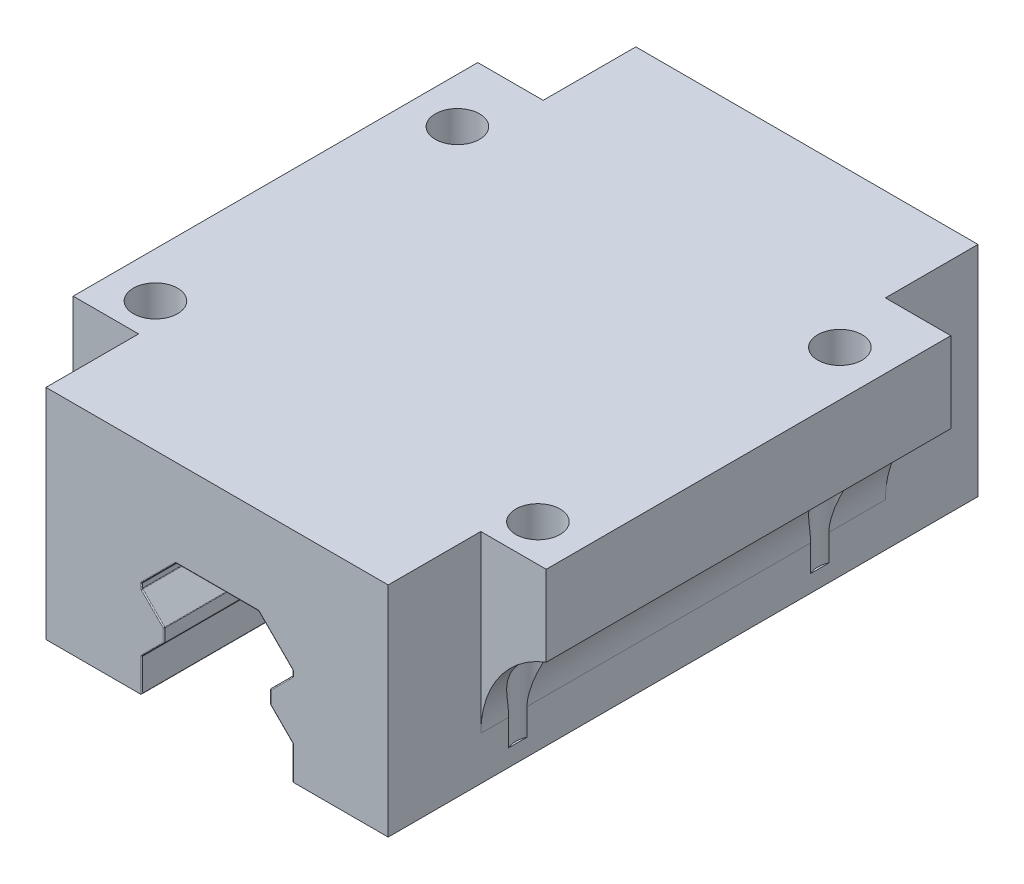
SolidWorks part; units mm, degrees
material "Серое литое железо (SN)"
ref_plane "Спереди" through (0, 0, 0) normal (0, 0, 1) x (1, 0, 0)
ref_plane "Сверху" through (0, 0, 0) normal (0, 1, 0) x (1, 0, 0)
ref_plane "Справа" through (0, 0, 0) normal (1, 0, 0) x (0, 0, -1)
sketch "Эскиз4" plane through (0, 0, 0) normal (0, 0, 1) x (1, 0, 0)
  line L1 (-17, 10.85) -> (17, 10.85)
  line L2 (-17, 10.85) -> (-17, -10.85)
  line L3 (-17, -10.85) -> (17, -10.85)
  line L4 (17, 10.85) -> (17, -10.85)
  line L5 (-17, 10.85) -> (17, -10.85) construction
  line L6 (-17, -10.85) -> (17, 10.85) construction
  point P0 (0, 0)
  dimension "D1" = 34
  dimension "D2" = 21.7
extrude "Бобышка-Вытянуть2" add sketch "Эскиз4" along normal blind 58.6
sketch "Эскиз5" plane through (0, 0, 0) normal (0, 0, -1) x (-1, 0, 0)
  line L0 (0, -10.85) -> (7.5, -10.85)
  line L1 (17, -10.85) -> (-17, -10.85) construction
  line L2 (7.5, -10.85) -> (7.5, -7.55)
  line L3 (7.5, -7.55) -> (5.26, -5.31)
  line L4 (5.26, -5.31) -> (5.26, -3.9893)
  line L5 (5.26, -3.9893) -> (7.5, -1.7493)
  line L6 (7.5, -1.7493) -> (7.5, -1.2493)
  line L7 (7.5, -1.2493) -> (4.1007, 2.15)
  line L8 (4.1007, 2.15) -> (-4.1007, 2.15)
  line L9 (-4.1007, 2.15) -> (-7.5, -1.2493)
  line L10 (-7.5, -1.2493) -> (-7.5, -1.7493)
  line L11 (-7.5, -1.7493) -> (-5.26, -3.9893)
  line L12 (-5.26, -3.9893) -> (-5.26, -5.31)
  line L13 (-5.26, -5.31) -> (-7.5, -7.55)
  line L14 (-7.5, -7.55) -> (-7.5, -10.85)
  line L15 (-7.5, -10.85) -> (0, -10.85)
  dimension "D1" = 7.5
  dimension "D2" = 7.5
  dimension "D3" = 3.3
  dimension "D4" = 135
  dimension "D5" = 135
  dimension "D6" = 135
  dimension "D7" = 135
  dimension "D8" = 135
  dimension "D9" = 135
  dimension "D10" = 135
  dimension "D11" = 135
  dimension "D12" = 135
  dimension "D13" = 135
  dimension "D14" = 0.5
  dimension "D15" = 13
  dimension "D16" = 15
  dimension "D17" = 10.52
extrude "Вырез-Вытянуть1" cut sketch "Эскиз5" against normal blind 58.6
fillet "Скругление1" radius 0.1 40 edges at (-5.8004, 0.4504, 58.6) (-5.8004, 0.4504, 0) (7.5, -9.2, 58.6) (7.5, -10.85, 29.3) (7.5, -9.2, 0) (6.38, -6.43, 58.6) (7.5, -7.55, 29.3) (6.38, -6.43, 0) (5.26, -4.6496, 58.6) (5.26, -5.31, 29.3) (5.26, -4.6496, 0) (6.38, -2.8693, 58.6) (5.26, -3.9893, 29.3) (6.38, -2.8693, 0) (7.5, -1.4993, 58.6) (7.5, -1.7493, 29.3) (7.5, -1.4993, 0) (5.8004, 0.4504, 58.6) (7.5, -1.2493, 29.3) (5.8004, 0.4504, 0) (-4.1007, 2.15, 29.3) (0, 2.15, 58.6) (4.1007, 2.15, 29.3) (0, 2.15, 0) (-7.5, -10.85, 29.3) (-7.5, -9.2, 58.6) (-7.5, -9.2, 0) (-7.5, -7.55, 29.3) (-6.38, -6.43, 58.6) (-6.38, -6.43, 0) (-5.26, -5.31, 29.3) (-5.26, -4.6496, 58.6) (-5.26, -4.6496, 0) (-5.26, -3.9893, 29.3) (-6.38, -2.8693, 58.6) (-6.38, -2.8693, 0) (-7.5, -1.7493, 29.3) (-7.5, -1.4993, 58.6) (-7.5, -1.2493, 29.3) (-7.5, -1.4993, 0)
sketch "Эскиз9" plane through (17, 0, 0) normal (1, 0, 0) x (0, 0, -1)
  line L0 (-29.3, 10.85) -> (-9.2, 10.85)
  line L1 (-58.6, 10.85) -> (0, 10.85) construction
  line L2 (-9.2, 10.85) -> (-9.2, 2.85)
  line L3 (-9.2, 2.85) -> (-49.4, 2.85)
  line L4 (-49.4, 2.85) -> (-49.4, 10.85)
  line L5 (-49.4, 10.85) -> (-29.3, 10.85)
  dimension "D1" = 20.1
  dimension "D2" = 8
extrude "Бобышка-Вытянуть4" add sketch "Эскиз9" along normal blind 6.5
sketch "Эскиз10" plane through (-17, 0, 0) normal (-1, 0, 0) x (0, 0, 1)
  line L0 (29.3, 10.85) -> (49.4, 10.85)
  line L1 (58.6, 10.85) -> (0, 10.85) construction
  line L2 (49.4, 10.85) -> (49.4, 2.85)
  line L3 (49.4, 2.85) -> (9.2, 2.85)
  line L4 (9.2, 2.85) -> (9.2, 10.85)
  line L5 (9.2, 10.85) -> (29.3, 10.85)
  dimension "D1" = 20.1
  dimension "D2" = 20.1
  dimension "D3" = 8
extrude "Бобышка-Вытянуть5" add sketch "Эскиз10" along normal blind 6.5
fillet "Скругление3" radius 10 1 edges at (-17, 2.85, 29.3)
fillet "Скругление4" radius 10 1 edges at (17, 2.85, 29.3)
sketch "Эскиз11" plane through (0, 10.85, 0) normal (0, 1, 0) x (1, 0, 0)
  line L5 (-19, -15.7232) -> (19, -45.7232) construction
  line L6 (-19, -45.7232) -> (19, -15.7232) construction
  circle A0 centre (-19, -15.7232) radius 2.2
  circle A1 centre (19, -15.7232) radius 2.2
  circle A2 centre (-19, -45.7232) radius 2.2
  circle A3 centre (19, -45.7232) radius 2.2
  point P0 (0, -30.7232)
  dimension "D1" = 30
  dimension "D2" = 38
extrude "Вырез-Вытянуть2" cut sketch "Эскиз11" against normal blind 20
